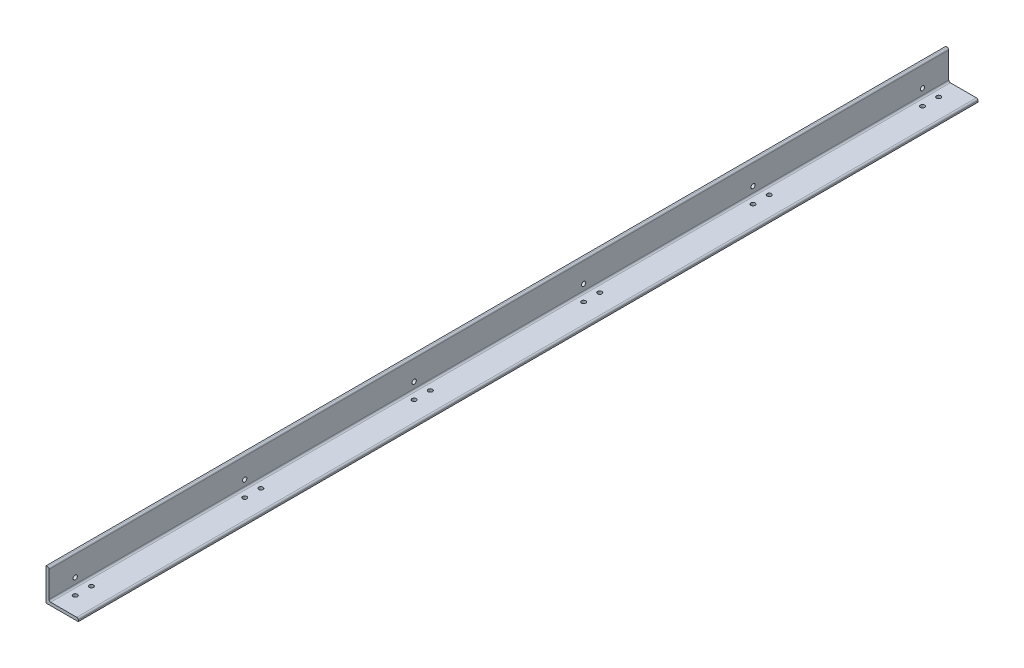
SolidWorks part; units mm, degrees
material "6061 Alloy"
ref_plane "Front Plane" through (0, 0, 0) normal (0, 0, 1) x (1, 0, 0)
ref_plane "Top Plane" through (0, 0, 0) normal (0, 1, 0) x (1, 0, 0)
ref_plane "Right Plane" through (0, 0, 0) normal (1, 0, 0) x (0, 0, -1)
sketch "Sketch1" plane through (0, 0, 0) normal (0, 0, 1) x (1, 0, 0)
  line L0 (0, 0) -> (0, 50.8)
  line L1 (0, 50.8) -> (4.7625, 50.8)
  line L2 (4.7625, 50.8) -> (4.7625, 4.7625)
  line L3 (4.7625, 4.7625) -> (50.8, 4.7625)
  line L4 (50.8, 4.7625) -> (50.8, 0)
  line L5 (50.8, 0) -> (0, 0)
  dimension "D1" = 50.8
  dimension "D2" = 50.8
  dimension "D3" = 4.7625
extrude "Boss-Extrude1" add sketch "Sketch1" along normal mid plane 1416.05
fillet "Fillet1" radius 2.54 3 edges at (50.8, 4.7625, 0) (4.7625, 4.7625, 0) (4.7625, 50.8, 0)
hole_wizard "1/4 Clearance Hole1" positions "Sketch9" profile "Sketch8" hole size "1/4" standard "ANSI Inch" end condition up to next
sketch "Sketch9" plane through (0, 4.7625, 0) normal (0, 1, 0) x (1, 0, 0)
  line L2 (48.26, -708.025) -> (7.3025, -708.025) construction
  line L4 (0, -708.025) -> (0, 708.025) construction
  point P1 (17.4625, -679.45)
  point P13 (17.4625, -654.05)
  dimension "D1" = 17.4625
  dimension "D2" = 28.575
  dimension "D3" = 25.4
sketch "Sketch8" plane through (17.4625, 4.7625, 679.45) normal (1, 0, 0) x (0, 0, 1)
  line L0 (0, 0) -> (0, 4.7625)
  line L1 (0, 4.7625) -> (3.3782, 4.7625)
  line L2 (3.3782, 4.7625) -> (3.3782, 0)
  line L5 (3.3782, 0) -> (0, 0)
  line L11 (0, -6.35) -> (0, 107.95) construction
  dimension "Thru Hole Dia." = 6.7564
  dimension "Thru Hole Depth" = 4.7625
pattern_linear "LPattern1" count 6 spacing 266.7 along (0, 0, -1) of "1/4 Clearance Hole1"
ref_plane "Plane1" through (0, 0, 0) normal (0.7071, -0.7071, 0) x (-0.7071, -0.7071, 0)
hole_wizard "1/4 Clearance Hole4" positions "Sketch17" profile "Sketch16" hole size "1/4" standard "ANSI Inch" end condition up to next
sketch "Sketch17" plane through (0, 0, 0) normal (-1, 0, 0) x (0, 0, 1)
  line L0 (-708.025, 16.6687) -> (-659.6641, 16.6687) construction
  line L1 (-708.025, 50.8) -> (-708.025, 0) construction
  line L2 (708.025, 0) -> (-708.025, 0) construction
  point P6 (-666.75, 16.6687)
  dimension "D1" = 41.275
  dimension "D2" = 16.6687
sketch "Sketch16" plane through (0, 16.6687, -666.75) normal (0, 1, 0) x (0, 0, 1)
  line L0 (0, 0) -> (0, 4.7625)
  line L1 (0, 4.7625) -> (3.3782, 4.7625)
  line L2 (3.3782, 4.7625) -> (3.3782, 0)
  line L5 (3.3782, 0) -> (0, 0)
  line L11 (0, -6.35) -> (0, 107.95) construction
  dimension "Thru Hole Dia." = 6.7564
  dimension "Thru Hole Depth" = 4.7625
pattern_linear "LPattern4" count 6 spacing 266.7 along (0, 0, 1) of "1/4 Clearance Hole4"
